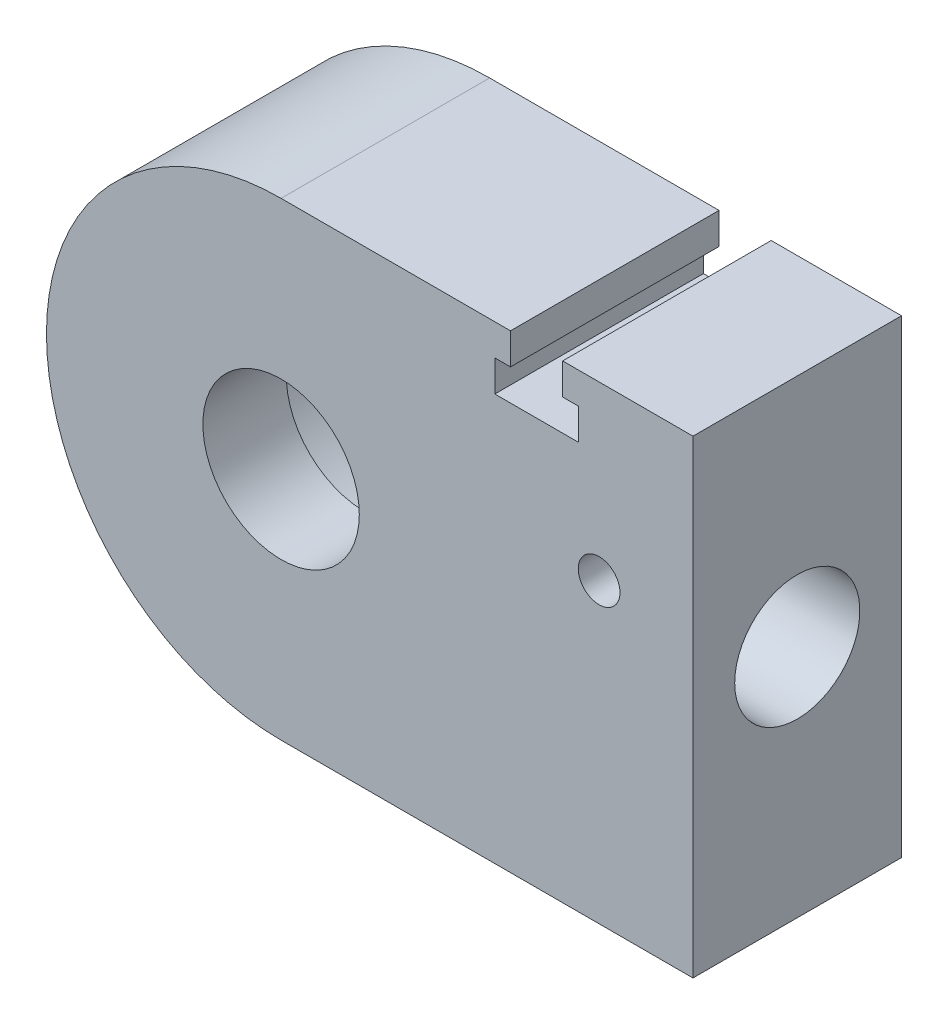
SolidWorks part; units mm, degrees
ref_plane "Plan de face" through (0, 0, 0) normal (0, 0, 1) x (1, 0, 0)
ref_plane "Plan de dessus" through (0, 0, 0) normal (0, 1, 0) x (1, 0, 0)
ref_plane "Plan de droite" through (0, 0, 0) normal (1, 0, 0) x (0, 0, -1)
sketch "Esquisse1" plane through (0, 0, 0) normal (0, 0, 1) x (1, 0, 0)
  line L0 (-634.5081, 20) -> (-595.0087, 20)
  line L1 (-595.0087, 20) -> (-595.0087, -25)
  line L2 (-595.0087, -25) -> (-634.5081, -25)
  line L3 (-666.113, -2.5) -> (-573.9627, -2.5) construction
  line L4 (-612.5087, 20) -> (-612.5087, 17)
  line L5 (-595.0087, -2.5) -> (-612.0087, -2.5)
  line L6 (-595.0087, -2.5) -> (-595.0087, 3.5)
  line L7 (-595.0087, 3.5) -> (-612.0087, 3.5)
  line L8 (-612.0087, -2.5) -> (-612.0087, 3.5)
  line L9 (-612.5087, 17) -> (-614.0087, 17)
  line L10 (-614.0087, 17) -> (-614.0087, 14)
  line L11 (-614.0087, 14) -> (-606.0087, 14)
  line L12 (-610.0087, 13.0932) -> (-610.0087, 21.3337) construction
  line L13 (-606.0087, 17) -> (-606.0087, 14)
  line L14 (-607.5087, 17) -> (-606.0087, 17)
  line L15 (-607.5087, 20) -> (-607.5087, 17)
  circle A0 centre (-634.5081, -2.5) radius 7.5
  arc A1 (-634.5081, 20) -> (-634.5081, -25) centre (-634.5081, -2.5) ccw
  circle A3 centre (-606.8206, -19.5) radius 4
  circle A5 centre (-634.5081, -2.5) radius 14
  circle A7 centre (-604.0087, 3.5) radius 2
  point P19 (-610.0087, 14)
  dimension "D1" = 6
  dimension "D3" = 8
  dimension "D4" = 17
  dimension "D5" = 28
  dimension "D6" = 15
  dimension "D8" = 8
  dimension "D9" = 5
  dimension "D11" = 4
  dimension "D12" = 8
  dimension "D13" = 3
  dimension "D2" = 17
  dimension "D7" = 45
  dimension "D10" = 39.4994
  dimension "D14" = 3
  dimension "D15" = 15
extrude "Boss.-Extru.1" add sketch "Esquisse1" along normal mid plane 20 contours L1 L2 A1 L0 | A0
revolve "Enlèvement de matière-Révolution1" cut sketch "Esquisse1<3>" angle 360 about L3
sketch "Esquisse1<3>" plane through (0, 0, 0) normal (0, 0, 1) x (1, 0, 0) same geometry as "Esquisse1"
extrude "Enlèv. mat.-Extru.1" cut sketch "Esquisse1<5>" against normal blind 10 and the other way blind 2 contours A5
sketch "Esquisse1<5>" plane through (0, 0, 0) normal (0, 0, 1) x (1, 0, 0) same geometry as "Esquisse1"
extrude "Enlèv. mat.-Extru.2" cut sketch "Esquisse1<6>" against normal through all both and the other way through all contours A7
sketch "Esquisse1<6>" plane through (0, 0, 0) normal (0, 0, 1) x (1, 0, 0) same geometry as "Esquisse1"
extrude "Enlèv. mat.-Extru.3" cut sketch "Esquisse1<7>" against normal through all both and the other way through all contours L0 L4 L9 L10 L11 region at (-610.0087, 16.6538, 0)
sketch "Esquisse1<7>" plane through (0, 0, 0) normal (0, 0, 1) x (1, 0, 0) same geometry as "Esquisse1"
